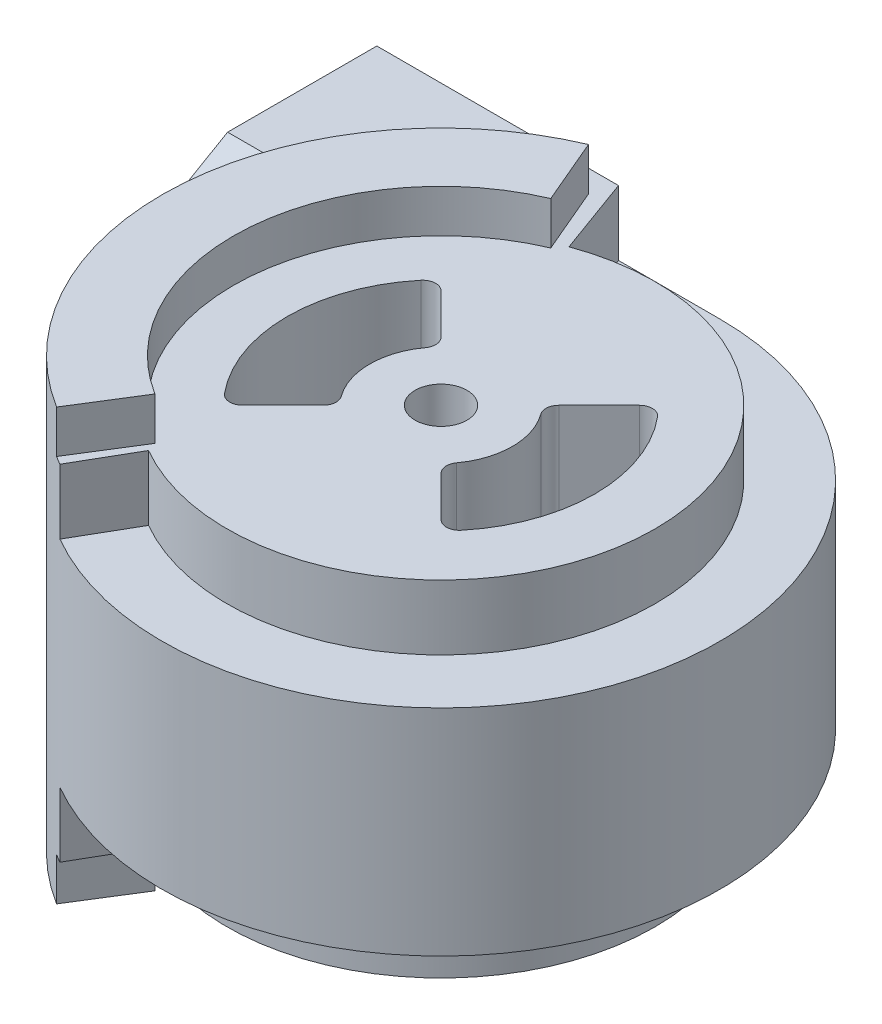
SolidWorks part; units mm, degrees
note: The reader was unsure of these and kept them because the rebuilt part matched: shared geometry of "Sketch2<3>".
ref_plane "Front Plane" through (0, 0, 0) normal (0, 0, 1) x (1, 0, 0)
ref_plane "Top Plane" through (0, 0, 0) normal (0, 1, 0) x (1, 0, 0)
ref_plane "Right Plane" through (0, 0, 0) normal (1, 0, 0) x (0, 0, -1)
sketch "Sketch1" plane through (0, 0, 0) normal (0, 1, 0) x (1, 0, 0)
  line L0 (0, 43) -> (-52.8952, 43)
  line L1 (-52.8952, 43) -> (-52.8952, -3)
  line L2 (-52.8952, -3) -> (-42.8952, -3)
  line L3 (0, 43) -> (0, -43) construction
  line L4 (-15.2789, -15.2789) -> (-9.083, -9.083)
  line L5 (-15.2789, 15.2789) -> (-9.083, 9.083)
  line L6 (-7.7782, 7.7782) -> (0, 0) construction
  line L7 (0, 0) -> (-7.7782, -7.7782) construction
  line L10 (15.2789, 15.2789) -> (9.083, 9.083)
  line L11 (15.2789, -15.2789) -> (9.083, -9.083)
  arc A0 (-42.8952, -3) -> (0, 43) centre (0, 0) ccw
  circle A1 centre (0, 0) radius 4
  arc A2 (-8.8822, 6.4889) -> (-8.8822, -6.4889) centre (0, 0) ccw
  arc A3 (-18.2317, 15.1425) -> (-18.2317, -15.1425) centre (0, 0) ccw
  arc A6 (-8.8822, 6.4889) -> (-9.083, 9.083) centre (-10.4972, 7.6687) ccw
  arc A7 (-9.083, -9.083) -> (-8.8822, -6.4889) centre (-10.4972, -7.6687) ccw
  arc A8 (-15.2789, -15.2789) -> (-18.2317, -15.1425) centre (-16.6931, -13.8647) cw
  arc A9 (-18.2317, 15.1425) -> (-15.2789, 15.2789) centre (-16.6931, 13.8647) cw
  arc A10 (18.2317, 15.1425) -> (15.2789, 15.2789) centre (16.6931, 13.8647) ccw
  arc A11 (15.2789, -15.2789) -> (18.2317, -15.1425) centre (16.6931, -13.8647) ccw
  arc A12 (9.083, -9.083) -> (8.8822, -6.4889) centre (10.4972, -7.6687) cw
  arc A13 (8.8822, 6.4889) -> (9.083, 9.083) centre (10.4972, 7.6687) cw
  arc A14 (18.2317, 15.1425) -> (18.2317, -15.1425) centre (0, 0) cw
  arc A15 (8.8822, 6.4889) -> (8.8822, -6.4889) centre (0, 0) cw
  point P24 (-16.7584, -16.7584)
  point P27 (-16.7584, 16.7584)
  point P36 (16.7584, 16.7584)
  point P37 (16.7584, -16.7584)
  dimension "D3" = 43
  dimension "D4" = 8
  dimension "D5" = 7
  dimension "D6" = 12.7
  dimension "D9" = 2
  dimension "D1" = 10
  dimension "D2" = 46
  dimension "D7" = 45
  dimension "D8" = 45
extrude "Boss-Extrude1" add sketch "Sketch1" along normal blind 26.56
sketch "Sketch2" plane through (0, 26.56, 0) normal (0, 1, 0) x (1, 0, 0)
  line L0 (-22.8798, -39.629) -> (-16.5, -28.5788)
  line L1 (-15.6507, 43) -> (-11.2867, 31.0099)
  line L2 (-11.2867, 31.0099) -> (0, 0) construction
  line L3 (0, 0) -> (-16.5, -28.5788) construction
  line L4 (0, 0) -> (-52.8952, 0) construction
  line L5 (-52.8952, 43) -> (-52.8952, -3) construction
  line L6 (0, 43) -> (-52.8952, 43) construction
  line L7 (-16.841, 39.5649) -> (-12.5328, 29.4437)
  line L8 (-16.9574, -27.1375) -> (-22.7865, -36.4661)
  line L9 (-16.9574, -27.1375) -> (0, 0) construction
  line L10 (0, 0) -> (-12.5328, 29.4437) construction
  arc A0 (-15.6507, 43) -> (-22.8798, -39.629) centre (0, 0) cw
  arc A1 (-16.5, -28.5788) -> (-11.2867, 31.0099) centre (0, 0) ccw
  arc A3 (-42.8952, -3) -> (0, 43) centre (0, 0) ccw construction
  arc A4 (-16.9574, -27.1375) -> (-12.5328, 29.4437) centre (0, 0) cw
  arc A5 (-22.7865, -36.4661) -> (-16.841, 39.5649) centre (0, 0) cw
  point P18 (-14.6869, 34.5043)
  arc M8 (-42.8952, -3) -> (0, 43) centre (0, 0) ccw
  line M9 (0, 43) -> (-52.8952, 43)
  dimension "D3" = 10
  dimension "D4" = 11
  dimension "D1" = 70
  dimension "D2" = 60
  dimension "D5" = 2
  dimension "D6" = 2
extrude "Cut-Extrude1" cut sketch "Sketch2" against normal blind 10 contours A1 L0 L1 M8 M9
extrude "Boss-Extrude2" add sketch "Sketch2<3>" along normal blind 6.6 contours A5 L8 A4 L7 M8
sketch "Sketch2<3>" plane through (0, 26.56, 0) normal (0, 1, 0) x (1, 0, 0) same geometry as "Sketch2"
mirror "Mirror1" about plane through (0, 0, 0) normal (0, 1, 0) of "Boss-Extrude2", "Cut-Extrude1", "Boss-Extrude1"
sketch "Sketch3" plane through (-52.8952, 0, 0) normal (-1, 0, 0) x (0, 0, 1)
  line L0 (-43, 0) -> (3, 0) construction
  line L1 (-43, 26.56) -> (-43, -26.56) construction
  line L2 (3, 26.56) -> (3, -26.56) construction
  line L3 (3, 26.56) -> (3, -26.56) construction
  line L6 (3, 13.2791) -> (-20, 26.5581)
  line L7 (-20, 26.5581) -> (-43, 13.2791) construction
  line L8 (-43, 13.2791) -> (-43, -13.2791)
  line L9 (-43, -13.2791) -> (-20, -26.5581) construction
  line L10 (-20, -26.5581) -> (3, -13.2791)
  line L11 (3, -13.2791) -> (3, 13.2791) construction
  line L18 (-20, -26.5581) -> (-21.7353, -27.56)
  line L19 (-21.7353, -27.56) -> (4, -27.56)
  line L20 (4, -27.56) -> (4, -12.7017)
  line L21 (4, -12.7017) -> (3, -13.2791)
  line L22 (3, 13.2791) -> (4, 12.7017)
  line L23 (4, 12.7017) -> (4, 27.56)
  line L24 (4, 27.56) -> (-21.7353, 27.56)
  line L25 (-21.7353, 27.56) -> (-19.9829, 26.5482)
  line L26 (-43, 26.56) -> (3, 26.56) construction
  line L27 (-43, -26.56) -> (3, -26.56) construction
  circle A0 centre (-20, 0) radius 23 construction
  dimension "D1" = 1
  dimension "D2" = 1
  dimension "D3" = 1
  dimension "D4" = 1
extrude "Cut-Extrude2" cut sketch "Sketch3" against normal up to vertex (10 mm away)
sketch "Sketch4" plane through (-52.8952, 0, 0) normal (-1, 0, 0) x (0, 0, 1)
  line L0 (3, 0) -> (-43, 0) construction
  line L1 (3, 13.2791) -> (3, -13.2791) construction
  line L2 (-43, 26.56) -> (-43, -26.56) construction
  circle A0 centre (-20, 0) radius 21
  dimension "D1" = 42
extrude "Cut-Extrude3" cut sketch "Sketch4" against normal blind 20
sketch "Sketch5" plane through (0, 0, -43) normal (0, 0, -1) x (-1, 0, 0)
  line L0 (0, 16.56) -> (0, -16.56) construction
  line L6 (15.6507, 16.56) -> (15.6507, -16.56) construction
  line L7 (15.6507, 16.56) -> (15.6507, 26.56) construction
  line L8 (15.6507, 0) -> (52.8952, 0) construction
  line L9 (52.8952, 26.56) -> (52.8952, -26.56) construction
  line L10 (15.6507, -14) -> (52.8952, -14)
  line L11 (15.6507, -14) -> (15.6507, 14)
  line L12 (15.6507, 14) -> (52.8952, 14)
  line L13 (52.8952, -14) -> (52.8952, 14)
  line L14 (15.6507, -14) -> (52.8952, 14) construction
  line L15 (15.6507, 14) -> (52.8952, -14) construction
  point P1 (34.273, 0)
  point P10 (0, 0)
  dimension "D1" = 28
extrude "Boss-Extrude3" add sketch "Sketch5" along normal blind 1.5
sketch "Sketch6" plane through (0, 0, 0) normal (0, 1, 0) x (1, 0, 0)
  line L0 (-32.8952, 20) -> (-52.8952, 20)
  line L2 (-20.8952, 32) -> (-20.8952, 44.5)
  line L3 (-52.8952, 44.5) -> (-15.6507, 44.5) construction
  line L5 (-32.8952, 20) -> (-52.8952, 20.0033) construction
  line L7 (-32.8952, 41) -> (-32.8952, -1) construction
  arc A1 (-32.8952, 20) -> (-20.8952, 32) centre (-32.8952, 32) ccw
  point P2 (0, 0)
  dimension "D1" = 12
sketch "Sketch7" plane through (0, 0, -44.5) normal (0, 0, -1) x (-1, 0, 0)
  circle A1 centre (20.8952, 0) radius 4
  point P2 (0, 0)
  dimension "D1" = 8
sweep "Cut-Sweep3" cut profiles "Sketch7" path "Sketch6"
